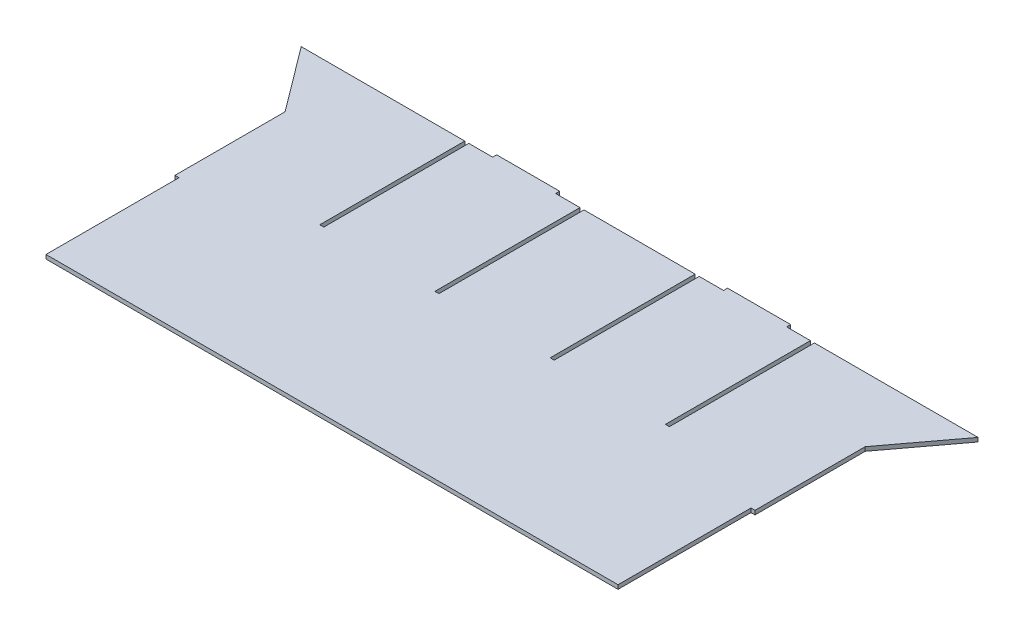
SolidWorks part; units mm, degrees
material "6061-T6 (SS)"
ref_plane "X-Y Datum" through (0, 0, 0) normal (0, 0, 1) x (1, 0, 0)
ref_plane "X-Z Datum" through (0, 0, 0) normal (0, 1, 0) x (1, 0, 0)
ref_plane "Y-Z Datum" through (0, 0, 0) normal (1, 0, 0) x (0, 0, -1)
sketch "Sketch1" plane through (0, 0, 0) normal (0, 0, 1) x (1, 0, 0)
  line L1 (-228.601, -1.5875) -> (228.601, -1.5875)
  line L2 (-228.601, -1.5875) -> (-228.601, 1.5875)
  line L3 (-228.601, 1.5875) -> (228.601, 1.5875)
  line L4 (228.601, -1.5875) -> (228.601, 1.5875)
  line L5 (-228.601, -1.5875) -> (228.601, 1.5875) construction
  line L6 (-228.601, 1.5875) -> (228.601, -1.5875) construction
  point P0 (0, 0)
  dimension "D1" = 3.175
  dimension "D2" = 457.202
extrude "Boss-Extrude1" add sketch "Sketch1" along normal blind 242.425
sketch "Sketch2" plane through (0, 1.5875, 0) normal (0, 1, 0) x (1, 0, 0)
  line L0 (228.601, 0) -> (225.426, 0)
  line L1 (228.601, 0) -> (-228.601, 0) construction
  line L2 (225.426, 0) -> (137.796, 0)
  line L3 (137.796, 0) -> (134.621, 0)
  line L10 (134.621, 0) -> (137.796, 0)
  line L11 (134.621, 0) -> (134.621, -114.3)
  line L12 (134.621, -114.3) -> (137.796, -114.3)
  line L13 (137.796, 0) -> (137.796, -114.3)
  line M2 (228.601, 0) -> (-228.601, 0)
  dimension "D1" = 87.63
  dimension "D2" = 3.175
  dimension "D3" = 114.3
  dimension "D4" = 3.175
extrude "Cut-Extrude1" cut sketch "Sketch2" against normal through all contours L13 L11 L12 M2 region at (136.2085, 1.5875, 57.15)
pattern_linear "LPattern1" count 4 spacing 90.807 along (-1, 0, 0) of "Cut-Extrude1"
sketch "Sketch3" plane through (0, 0, 0) normal (0, 0, -1) x (-1, 0, 0)
  line L1 (-115.8495, 1.5875) -> (-66.1907, 1.5875)
  line L2 (-115.8495, 1.5875) -> (-115.8495, -1.5875)
  line L3 (-115.8495, -1.5875) -> (-66.1907, -1.5875)
  line L4 (-66.1907, 1.5875) -> (-66.1907, -1.5875)
  line L5 (66.1907, 1.5875) -> (115.8495, 1.5875)
  line L6 (66.1907, 1.5875) -> (66.1907, -1.5875)
  line L7 (66.1907, -1.5875) -> (115.8495, -1.5875)
  line L8 (115.8495, 1.5875) -> (115.8495, -1.5875)
extrude "Boss-Extrude2" add sketch "Sketch3" along normal blind 3.175
sketch "Sketch4" plane through (0, -1.5875, 0) normal (0, -1, 0) x (1, 0, 0)
  line L0 (-228.601, 0) -> (-266.701, 0)
  line L1 (-266.701, 0) -> (-228.601, 50.8)
  line L2 (-228.601, 242.425) -> (-228.601, 0) construction
  line L3 (-228.601, 50.8) -> (-228.601, 0)
  dimension "D1" = 38.1
  dimension "D2" = 50.8
extrude "Boss-Extrude3" add sketch "Sketch4" against normal blind 3.175
mirror "Mirror1" about plane through (0, 0, 0) normal (1, 0, 0) of "Boss-Extrude3"
sketch "Sketch5" plane through (0, -1.5875, 0) normal (0, -1, 0) x (1, 0, 0)
  line L1 (-228.601, 242.425) -> (-225.426, 242.425)
  line L2 (-228.601, 242.425) -> (-228.601, 137.65)
  line L3 (-228.601, 137.65) -> (-225.426, 137.65)
  line L4 (-225.426, 242.425) -> (-225.426, 137.65)
  dimension "D1" = 3.175
  dimension "D2" = 104.775
extrude "Cut-Extrude2" cut sketch "Sketch5" against normal blind 3.175
mirror "Mirror2" about plane through (0, 0, 0) normal (1, 0, 0) of "Cut-Extrude2"
